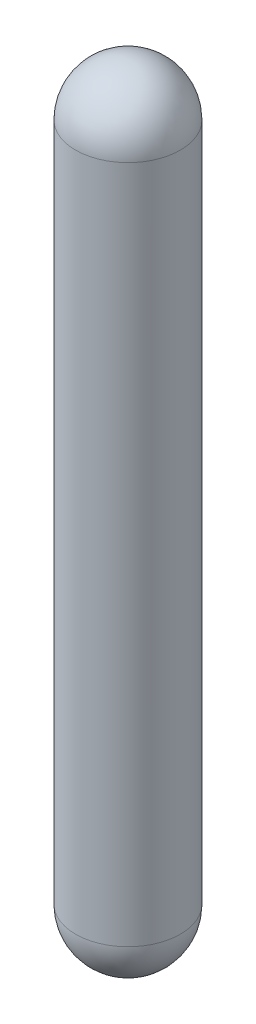
SolidWorks part; units mm, degrees
note: The reader was unsure of these and kept them because the rebuilt part matched: shared geometry of "Sketch1<4>".
ref_plane "Front Plane" through (0, 0, 0) normal (0, 0, 1) x (1, 0, 0)
ref_plane "Top Plane" through (0, 0, 0) normal (0, 1, 0) x (1, 0, 0)
ref_plane "Right Plane" through (0, 0, 0) normal (1, 0, 0) x (0, 0, -1)
sketch "Sketch1"
  line L0 (-114.7826, 1729.74) -> (-114.7826, 0)
  line L1 (-130.0226, 1729.74) -> (-130.0226, 0)
  line L2 (-133.35, 0) -> (-133.35, 1729.74)
  line L3 (0, 50.358) -> (0, -222.3667) construction
  line L6 (0, 1863.09) -> (0, 1859.7626)
  line L7 (0, 1844.5226) -> (0, 1859.7626)
  line L9 (-3.175, -158.5987) -> (-6.35, -158.5987)
  line L10 (-6.35, -158.5987) -> (-6.35, -129.8674)
  line L11 (-3.175, -114.7387) -> (-3.175, -158.5987)
  arc A0 (-114.7826, 1729.74) -> (0, 1844.5226) centre (0, 1729.74) cw
  arc A1 (-130.0226, 1729.74) -> (0, 1859.7626) centre (0, 1729.74) cw
  arc A2 (-133.35, 1729.74) -> (0, 1863.09) centre (0, 1729.74) cw
  arc A3 (-114.7826, 0) -> (-3.175, -114.7387) centre (0, 0) ccw
  arc A4 (-130.0226, 0) -> (-6.35, -129.8674) centre (0, 0) ccw
  arc A5 (-133.35, 0) -> (-6.35, -133.1987) centre (0, 0) ccw
  point P14 (-3.175, -130.6117)
  dimension "D5" = 133.35
  dimension "D4" = 1729.74
  dimension "D1" = 133.35
  dimension "D2" = 3.3274
  dimension "D3" = 15.24
  dimension "D7" = 3.175
  dimension "D8" = 25.4
  dimension "D6" = 15.873
  dimension "D9" = 3.175
sketch "Sketch1<4>" plane through (0, 0, 0) normal (0, 0, 1) x (1, 0, 0) same geometry as "Sketch1"
revolve "Revolve1" add sketch "Sketch1" angle 360 about L3
revolve "Revolve2" add sketch "Sketch1<4>" angle 360 about L3
equation "\"OD\"= 5.25'outside diameter"
equation "\"D1@Sketch1\"=\"OD\""
equation "\"t_wrap\"= 0.131'carbon fiber thickness"
equation "\"D2@Sketch1\"=\"t_wrap\""
equation "\"t_wall\"= 0.6'aluminum thickness"
equation "\"D3@Sketch1\"=\"t_wall\""
equation "\"D5@Sketch1\"=\"OD\""
